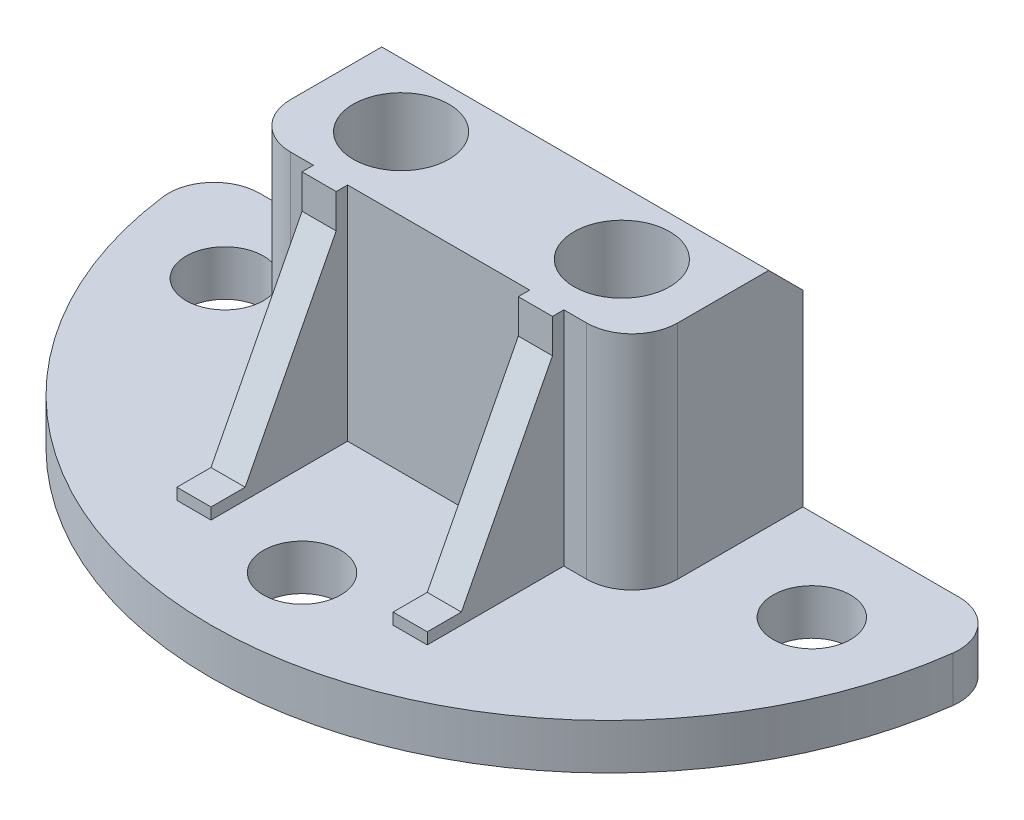
SolidWorks part; units mm, degrees
ref_plane "Front Plane" through (0, 0, 0) normal (0, 0, 1) x (1, 0, 0)
ref_plane "Top Plane" through (0, 0, 0) normal (0, 1, 0) x (1, 0, 0)
ref_plane "Right Plane" through (0, 0, 0) normal (1, 0, 0) x (0, 0, -1)
sketch "Sketch1" plane through (0, 0, 0) normal (0, 1, 0) x (1, 0, 0)
  line L0 (-17.5, 0) -> (17.5, 0)
  line L1 (-4.85, -4.3) -> (4.85, -4.3) construction
  line L2 (-12.8938, -4) -> (12.8938, -4) construction
  line L3 (-8.5, 7.5) -> (8.5, 7.5)
  line L4 (-8.5, 7.5) -> (-8.5, -7.5)
  line L5 (-8.5, -7.5) -> (8.5, -7.5)
  line L6 (8.5, 7.5) -> (8.5, -7.5)
  line L7 (-8.5, 7.5) -> (8.5, -7.5) construction
  line L8 (-8.5, -7.5) -> (8.5, 7.5) construction
  line L9 (12.8938, -4) -> (0, -13.5) construction
  line L10 (0, -13.5) -> (-12.8938, -4) construction
  circle A0 centre (0, 0) radius 17.5
  circle A1 centre (-4.85, -4.3) radius 2.1
  circle A2 centre (4.85, -4.3) radius 2.1
  circle A3 centre (12.8938, -4) radius 1.7
  circle A4 centre (0, -13.5) radius 1.7
  circle A5 centre (-12.8938, -4) radius 1.7
  circle A6 centre (0, 0) radius 13.5
  point P6 (0, 0)
  point P10 (0, -4.3)
  point P19 (13.2483, -3.7575)
  dimension "D3" = 35
  dimension "D6" = 4.2
  dimension "D7" = 3.4
  dimension "D8" = 4
  dimension "D1" = 9.7
  dimension "D2" = 4.3
  dimension "D4" = 17
  dimension "D5" = 15
  dimension "D9" = 4
extrude "Boss-Extrude1" add sketch "Sketch1" along normal blind 2 contours A4 A6 A3 L0 L6 L5 L4 A5 | A6 A4 A5 L0 A0 A3 region at (13.1482, 0, 1.1521) region at (15.5, 0, 0.3913)
extrude "Boss-Extrude2" add sketch "Sketch1<3>" along normal blind 11.75 contours L6 L0 L4 L5 A2 A1 | A1 | A2 region at (0, 0, 3.5973) region at (-4.85, 0, 4.3) region at (4.85, 0, 4.3)
sketch "Sketch1<3>" plane through (0, 0, 0) normal (0, 1, 0) x (1, 0, 0) same geometry as "Sketch1"
fillet "Fillet1" radius 2 4 edges at (-17.5, 1, 0) (-8.5, 6.875, 7.5) (8.5, 6.875, 7.5) (17.5, 1, 0)
chamfer "Chamfer1" distance 1.5 angle 45 1 edges at (0, 11.75, 0)
sketch "Sketch2" plane through (0, 0, 7.5) normal (0, 0, 1) x (1, 0, 0)
  line L0 (17.3537, 2) -> (-17.3537, 2) construction
  line L1 (-5.5, 11.75) -> (-4, 11.75)
  line L2 (-5.5, 11.75) -> (-5.5, 2)
  line L3 (-5.5, 2) -> (-4, 2)
  line L4 (-4, 11.75) -> (-4, 2)
  line L5 (-6.5, 2) -> (6.5, 2) construction
  line L6 (4, 11.75) -> (5.5, 11.75)
  line L7 (4, 11.75) -> (4, 2)
  line L8 (4, 2) -> (5.5, 2)
  line L9 (5.5, 11.75) -> (5.5, 2)
  line L10 (-4, 6.875) -> (4, 6.875) construction
  line L11 (-6.5, 11.75) -> (6.5, 11.75) construction
  point P14 (0, 6.875)
  dimension "D2" = 8
  dimension "D3" = 1.5
extrude "Boss-Extrude3" add sketch "Sketch2" along normal blind 6
sketch "Sketch3" plane through (5.5, 0, 0) normal (1, 0, 0) x (0, 0, -1)
  line L0 (-8, 11.75) -> (-8, 10.25)
  line L1 (-13.5, 11.75) -> (-7.5, 11.75) construction
  line L2 (-8, 10.25) -> (-12, 2.5)
  line L3 (-12, 2.5) -> (-13.5, 2.5)
  line L4 (-13.5, 2) -> (-13.5, 11.75) construction
  line L5 (-13.5, 2.5) -> (-13.5, 2)
  line L6 (-13.5, 2) -> (-7.5, 2)
  line L7 (-7.5, 2) -> (-7.5, 11.75)
  line L8 (-7.5, 11.75) -> (-8, 11.75)
  line L9 (-13.5, 2.5) -> (-13.5, 11.75)
  line L10 (-13.5, 11.75) -> (-8, 11.75)
  point P14 (-7.5, 14)
  line M6 (-7.5, 11.75) -> (-13.5, 11.75)
  line M7 (-13.5, 11.75) -> (-13.5, 2)
  dimension "D1" = 1.5
  dimension "D2" = 0.5
extrude "Cut-Extrude1" cut sketch "Sketch3" against normal through all contours L3 L2 L0 M6 M7 region at (5.5, 8.0196, 11.3707)
extrude "Cut-Extrude2" cut sketch "Sketch1<4>" against normal blind 5 from surface contours A1 | A2 starting at face at (0, 11.75, 6.5592)
sketch "Sketch1<4>" plane through (0, 0, 0) normal (0, 1, 0) x (1, 0, 0) same geometry as "Sketch1"
